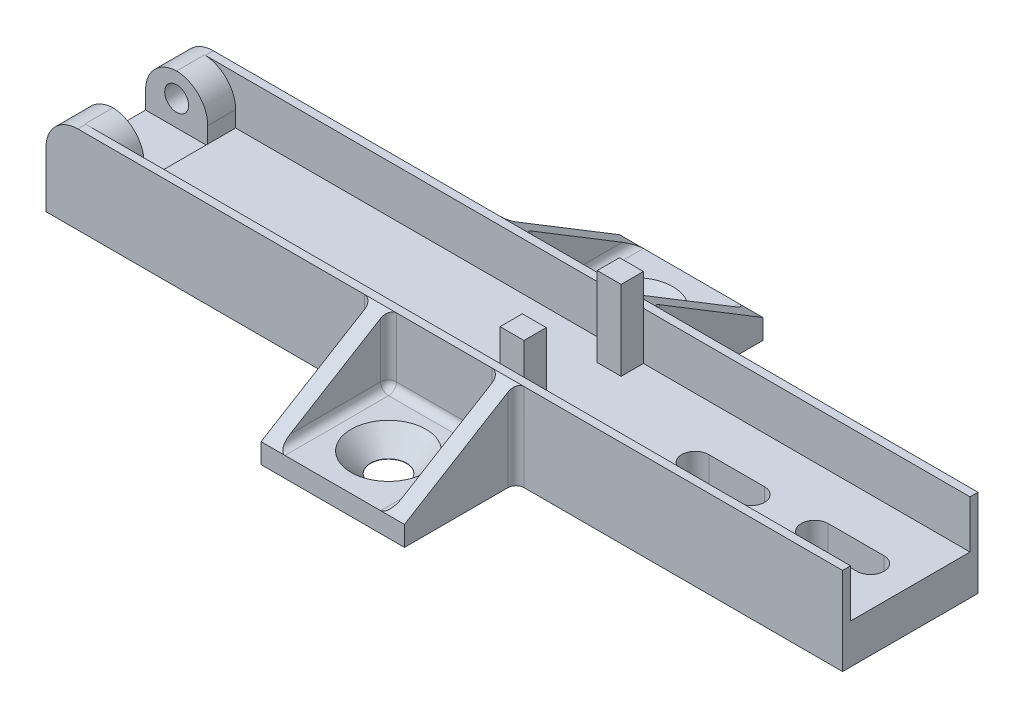
SolidWorks part; units mm, degrees
ref_plane "Ebene vorne" through (0, 0, 0) normal (0, 0, 1) x (1, 0, 0)
ref_plane "Ebene oben" through (0, 0, 0) normal (0, 1, 0) x (1, 0, 0)
ref_plane "Ebene rechts" through (0, 0, 0) normal (1, 0, 0) x (0, 0, -1)
sketch "Sketch1" plane through (0, 0, 0) normal (0, 1, 0) x (1, 0, 0)
  line L0 (-50, -7.5) -> (-50, 7.5)
  line L1 (-50, -7.5) -> (50, -7.5)
  line L2 (-50, 7.5) -> (50, 7.5)
  line L3 (50, -7.5) -> (50, 7.5)
  line L4 (-50, -7.5) -> (50, 7.5) construction
  line L5 (-50, 7.5) -> (50, -7.5) construction
  point P1 (0, 0)
  dimension "D1" = 15
  dimension "D2" = 100
extrude "Boss-Extrude1" add sketch "Sketch1" along normal blind 5
sketch "Sketch2" plane through (0, 5, 0) normal (0, 1, 0) x (1, 0, 0)
  line L0 (-50, -7.5) -> (50, -7.5) construction
  line L1 (-50, 7.5) -> (-42.1952, 7.5)
  line L2 (-50, 7.5) -> (-50, -7.5)
  line L3 (-50, -7.5) -> (-42.1952, -7.5)
  line L4 (-42.1952, 7.5) -> (-42.1952, -7.5)
extrude "Boss-Extrude2" add sketch "Sketch2" along normal blind 6
sketch "Sketch3" plane through (0, 0, 7.5) normal (0, 0, 1) x (1, 0, 0)
  line L1 (-42.1952, 8) -> (-50, 8) construction
  line L2 (-42.1952, 11) -> (-42.1952, 5) construction
  line L3 (-50, 11) -> (-50, 0) construction
  circle A0 centre (-46.0976, 8) radius 1.5
  dimension "D1" = 3
extrude "Cut-Extrude1" cut sketch "Sketch3" against normal up to surface (15 mm away) up to face at (-14.0651, 5.3333, -7.5)
fillet "Fillet1" radius 4 1 edges at (-42.1952, 11, 0)
sketch "Sketch4" plane through (0, 11, 0) normal (0, 1, 0) x (1, 0, 0)
  line L0 (-42.1952, 0) -> (-50, 0) construction
  line L1 (-42.1952, -7.5) -> (-42.1952, 7.5) construction
  line L2 (-50, 7.5) -> (-50, -7.5) construction
  line L3 (-50, -4) -> (-42.1952, -4)
  line L4 (-50, -4) -> (-50, 4)
  line L5 (-42.1952, -4) -> (-42.1952, 4)
  line L6 (-50, 4) -> (-42.1952, 4)
  line L7 (-50, -4) -> (-42.1952, 4) construction
  line L8 (-42.1952, -4) -> (-50, 4) construction
  point P7 (-46.0976, 0)
  dimension "D1" = 8
extrude "Cut-Extrude2" cut sketch "Sketch4" against normal blind 6.2
sketch "Sketch5" plane through (0, 0, 0) normal (0, -1, 0) x (1, 0, 0)
  line L0 (45, 0) -> (38, 0) construction
  line L1 (45, -1.7) -> (38, -1.7)
  line L2 (45, 1.7) -> (38, 1.7)
  line L3 (30, 0) -> (23, 0) construction
  line L4 (30, -1.7) -> (23, -1.7)
  line L5 (30, 1.7) -> (23, 1.7)
  line L7 (50, 7.5) -> (50, -7.5) construction
  arc A0 (45, -1.7) -> (45, 1.7) centre (45, 0) ccw
  arc A1 (38, 1.7) -> (38, -1.7) centre (38, 0) ccw
  arc A2 (30, -1.7) -> (30, 1.7) centre (30, 0) ccw
  arc A3 (23, 1.7) -> (23, -1.7) centre (23, 0) ccw
  point P3 (41.5, 0)
  point P8 (26.5, 0)
  dimension "D2" = 15
  dimension "^3,4" = 3.4
  dimension "D3" = 3.4
  dimension "D4" = 5
  dimension "D5" = 7
  dimension "D6" = 7
extrude "Cut-Extrude3" cut sketch "Sketch5" against normal up to surface (5 mm away) up to face at (-11.4635, 5, 0)
sketch "Sketch6" plane through (0, 5, 0) normal (0, 1, 0) x (1, 0, 0)
  line L0 (-50, 4) -> (-50, -4) construction
  line L1 (-26, 7.5) -> (-26, -7.5) construction
  line L2 (50, 7.5) -> (-42.1952, 7.5) construction
  line L3 (-42.1952, -7.5) -> (50, -7.5) construction
  circle A0 centre (-26, 0) radius 2.5
  point P10 (-26, 0)
  dimension "D1" = 5
  dimension "D2" = 24
extrude "Boss-Extrude3" [suppressed] add sketch "Sketch6" along normal blind 15
sketch "Sketch7" plane through (0, 5, 0) normal (0, 1, 0) x (1, 0, 0)
  line L0 (-42.1952, -7.5) -> (50, -7.5) construction
  line L1 (6, -7.5) -> (9, -7.5)
  line L2 (6, -7.5) -> (6, -4.7)
  line L3 (6, -4.7) -> (9, -4.7)
  line L4 (9, -7.5) -> (9, -4.7)
  line L5 (0, 0) -> (16.5077, 0) construction
  line L6 (50, -7.5) -> (50, 7.5) construction
  line L7 (9, 7.5) -> (9, 4.7)
  line L8 (6, 4.7) -> (9, 4.7)
  line L9 (6, 7.5) -> (6, 4.7)
  line L10 (6, 7.5) -> (9, 7.5)
  dimension "D1" = 2.8
  dimension "D2" = 3
  dimension "D3" = 41
extrude "Boss-Extrude4" add sketch "Sketch7" along normal blind 10
sketch "Sketch8" plane through (0, 0, 7.5) normal (0, 0, 1) x (1, 0, 0)
  line L1 (50, 0) -> (-50, 0)
  line L2 (50, 0) -> (50, 11)
  line L3 (50, 11) -> (-50, 11)
  line L4 (-50, 0) -> (-50, 11)
extrude "Boss-Extrude5" add sketch "Sketch8" along normal blind 1
mirror "Mirror1" about plane through (0, 0, 0) normal (0, 0, 1) of "Boss-Extrude5"
fillet "Fillet2" radius 4 2 edges at (-50, 11, 6.25) (-50, 11, -6.25)
sketch "Sketch9" plane through (0, 0, 8.5) normal (0, 0, 1) x (1, 0, 0)
  line L0 (-50, 0) -> (50, 0) construction
  line L1 (-9, 0) -> (9, 0)
  line L2 (-9, 0) -> (-9, 2.5)
  line L3 (-9, 2.5) -> (9, 2.5)
  line L4 (9, 0) -> (9, 2.5)
  dimension "D1" = 2.5
  dimension "D2" = 18
extrude "Boss-Extrude6" add sketch "Sketch9" along normal blind 14
ref_plane "Plane1" through (0, 0, 0) normal (-1, 0, 0) x (0, 0, 1)
sketch "Sketch10" plane through (9, 0, 0) normal (1, 0, 0) x (0, 0, -1)
  line L0 (-8.5, 11) -> (-22.5, 2.5)
  line L1 (-22.5, 2.5) -> (-8.5, 2.5) construction
  line L2 (-22.5, 2.5) -> (-8.5, 2.5)
  line L3 (-8.5, 0) -> (-8.5, 11) construction
  line L4 (-8.5, 2.5) -> (-8.5, 11)
  point P5 (0, 0)
extrude "Boss-Extrude7" add sketch "Sketch10" against normal blind 2
mirror "Mirror2" about plane through (0, 0, 0) normal (-1, 0, 0) of "Boss-Extrude7"
hole_wizard "CSK for M4 Countersunk Flat Head Screw1" positions "Sketch13" profile "Sketch12" countersink size "M4" standard "DIN" end condition up to next
sketch "Sketch13" plane through (0, 2.5, 0) normal (0, 1, 0) x (1, 0, 0)
  line L0 (7, -15.5) -> (-7, -15.5) construction
  line L1 (7, -22.5) -> (7, -8.5) construction
  line L2 (-7, -22.5) -> (-7, -8.5) construction
  point P9 (0, -15.5)
sketch "Sketch12" plane through (0, 2.5, 15.5) normal (1, 0, 0) x (0, 0, 1)
  line L0 (0, 0) -> (0, 2.501)
  line L1 (0, 2.501) -> (2.25, 2.501)
  line L2 (2.25, 2.501) -> (2.25, 2.45)
  line L3 (2.25, 2.45) -> (4.7, 0)
  line L5 (4.7, 0) -> (0, 0)
  line L6 (-2.25, 2.45) -> (-4.7, 0) construction
  line L11 (0, -6.35) -> (0, 107.95) construction
  dimension "Thru Hole Dia." = 4.5
  dimension "Thru Hole Depth" = 2.501
  dimension "Near C'Sink Dia." = 9.4
  dimension "Near C'Sink Angle" = 90
mirror "Mirror5" about plane through (0, 0, 0) normal (0, 0, 1) of "CSK for M4 Countersunk Flat Head Screw1", "Mirror2", "Boss-Extrude7", "Boss-Extrude6"
fillet "Fillet4" radius 1 14 edges at (-7, 6.75, 8.5) (7, 6.75, 8.5) (9, 5.5, 8.5) (-9, 5.5, 8.5) (-7, 2.5, 15.5) (7, 2.5, 15.5) (0, 2.5, 8.5) (9, 5.5, -8.5) (-9, 5.5, -8.5) (7, 6.75, -8.5) (-7, 6.75, -8.5) (0, 2.5, -8.5) (-7, 2.5, -15.5) (7, 2.5, -15.5)
